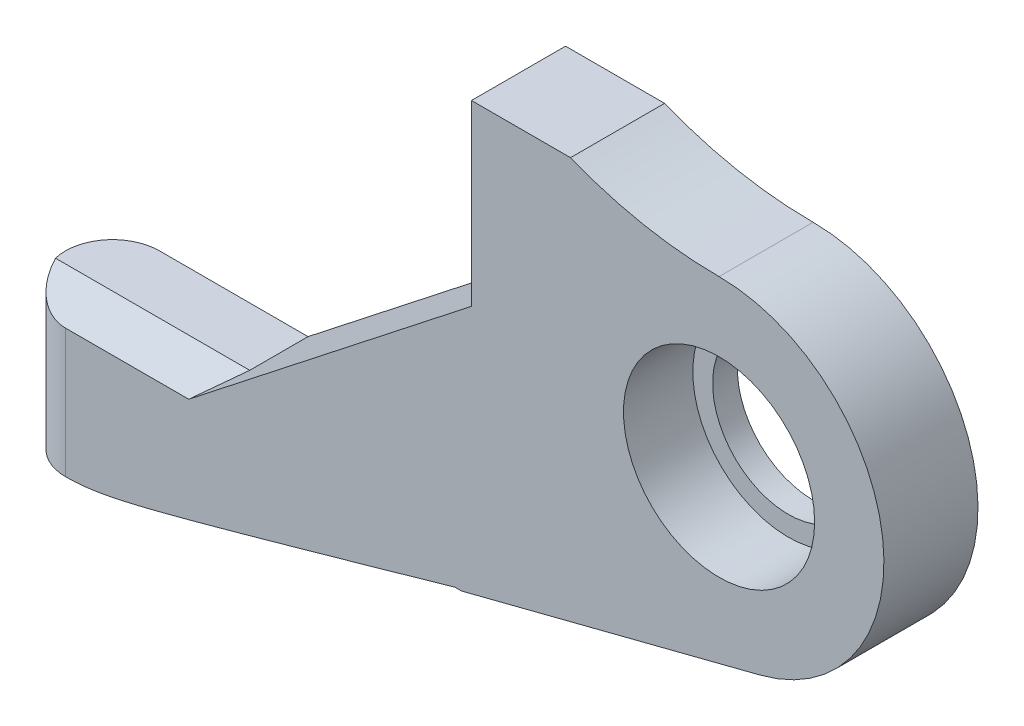
SolidWorks part; units mm, degrees
ref_plane "Top Plane" through (0, 0, 0) normal (0, 0, 1) x (1, 0, 0)
ref_plane "Right Plane" through (0, 0, 0) normal (0, 1, 0) x (1, 0, 0)
ref_plane "Front Plane" through (0, 0, 0) normal (1, 0, 0) x (0, 0, -1)
sketch "Sketch1" plane through (0, 0, 0) normal (0, 0, 1) x (1, 0, 0)
  line L0 (-49.65, -48.5) -> (-34.65, -48.5)
  line L1 (-34.65, -48.5) -> (6.0726, -16.5505)
  line L2 (-49.65, -48.5) -> (-49.65, -53.5)
  line L3 (-49.65, -53.5) -> (-9.65, -53.5)
  line L4 (-9.65, -53.5) -> (20.4828, -45.7789)
  line L5 (-49.65, -18.7122) -> (-49.65, -30) construction
  line L6 (-43.65, -30) -> (-43.65, -16) construction
  line L7 (-49.65, -30) -> (-43.65, -30) construction
  arc A0 (20.4828, -45.7789) -> (6.0726, -16.5505) centre (16.35, -29.65) ccw
  arc A1 (6.0726, -16.5505) -> (20.4828, -45.7789) centre (16.35, -29.65) ccw construction
  circle A2 centre (16.35, -29.65) radius 3.1
  arc A3 (20.8758, -46.7099) -> (30.7828, -19.4905) centre (16.35, -29.65) ccw construction
  circle A4 centre (16.35, -29.65) radius 3.1 construction
  dimension "D1" = 1
  dimension "D2" = 9
  dimension "D3" = 18.5
  dimension "D4" = 5
  dimension "D5" = 40
extrude "Boss-Extrude1" add sketch "Sketch1" along normal mid plane 9.5
sketch "Sketch2" plane through (0, -53.5, 0) normal (0, -1, 0) x (1, 0, 0)
  line L0 (-49.65, -4.75) -> (-49.65, 4.75)
  arc A0 (-49.65, -4.75) -> (-49.65, 4.75) centre (-49.65, 0) cw
extrude "Boss-Extrude2" add sketch "Sketch2" against normal up to surface (5 mm away) up to face at (-42.15, -48.5, 0)
sketch "Sketch3" plane through (0, -53.5, 0) normal (0, -1, 0) x (1, 0, 0)
  circle A0 centre (-49.65, 0) radius 4.75
  circle A1 centre (-49.65, 0) radius 3.25
  dimension "D1" = 6.5
extrude "Boss-Extrude3" add sketch "Sketch3" along normal blind 10
chamfer "Chamfer1" distance 10 angle 74 1 edges at (-44.9, -53.5, 0) first distance on face at (-49.65, -51, 0)
sketch "Sketch4" plane through (0, 0, 4.75) normal (0, 0, 1) x (1, 0, 0)
  circle A0 centre (16.35, -29.65) radius 9.65
  dimension "D1" = 19.3
extrude "Cut-Extrude1" cut sketch "Sketch4" against normal through all
sketch "Sketch5" plane through (0, 0, -4.75) normal (0, 0, 1) x (1, 0, 0)
  circle A0 centre (16.35, -29.65) radius 9.65
  circle A1 centre (16.35, -29.65) radius 9.65 construction
  circle A2 centre (16.35, -29.65) radius 7.65
  dimension "D1" = 2
extrude "Boss-Extrude4" add sketch "Sketch5" along normal offset from surface (2.5 mm away) 7 up to face at (26, -29.65, 4.75)
chamfer "Chamfer2" distance 2 angle 61 1 edges at (-42.15, -48.5, 4.75) tangent propagation no first distance on face at (26, -29.65, 4.75)
sketch "Sketch6" plane through (0, 0, -4.75) normal (0, 0, -1) x (-1, 0, 0)
  line L0 (8.65, -28.1013) -> (8.65, -10.1)
  line L1 (-6.0726, -16.5505) -> (34.65, -48.5) construction
  line L2 (8.65, -10.1) -> (-1.35, -10.1)
  line L3 (8.65, -28.1013) -> (-16.35, -13)
  line L4 (75, -10) -> (-10.5, -10) construction
  line L5 (-16.35, -29.65) -> (-16.35, -13) construction
  arc A0 (-1.35, -10.1) -> (-16.35, -13) centre (-16.35, 27.2431) cw
  arc A1 (-6.0726, -16.5505) -> (-20.4828, -45.7789) centre (-16.35, -29.65) ccw construction
  point P10 (-16.35, -29.65)
  dimension "D1" = 0.1
  dimension "D2" = 25
  dimension "D3" = 10
extrude "Boss-Extrude5" add sketch "Sketch6" against normal up to surface (9.5 mm away) up to face at (26, -29.65, 4.75)
